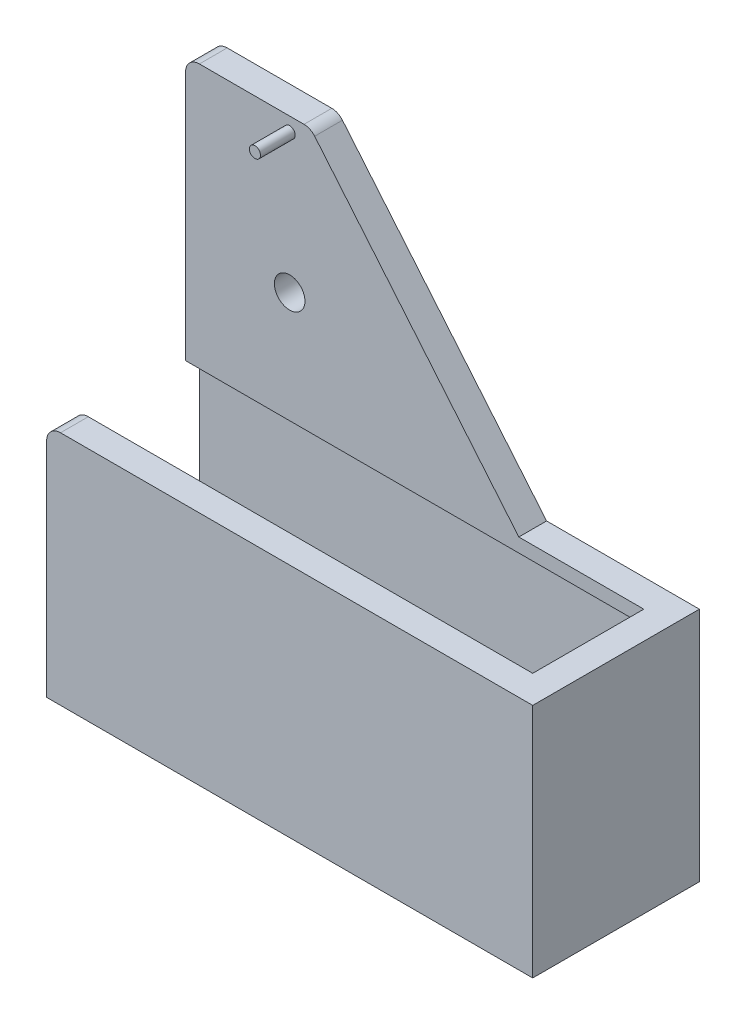
SolidWorks part; units mm, degrees
ref_plane "Front Plane" through (0, 0, 0) normal (0, 0, 1) x (1, 0, 0)
ref_plane "Top Plane" through (0, 0, 0) normal (0, 1, 0) x (1, 0, 0)
ref_plane "Right Plane" through (0, 0, 0) normal (1, 0, 0) x (0, 0, -1)
sketch "Sketch1" plane through (0, 0, 0) normal (0, 1, 0) x (1, 0, 0)
  line L1 (-165, 60) -> (165, 60)
  line L2 (-165, 60) -> (-165, -60)
  line L3 (-165, -60) -> (165, -60)
  line L4 (165, 60) -> (165, -60)
  line L5 (-165, 60) -> (165, -60) construction
  line L6 (-165, -60) -> (165, 60) construction
  point P0 (0, 0)
  dimension "D1" = 120
  dimension "D2" = 330
extrude "Boss-Extrude1" add sketch "Sketch1" along normal blind 120
sketch "Sketch2" plane through (165, 0, 0) normal (1, 0, 0) x (0, 0, -1)
  line L0 (0, 120) -> (0, 0) construction
  line L1 (-60, 120) -> (60, 120) construction
  line L2 (-60, 60) -> (60, 60) construction
  line L3 (-60, 120) -> (-60, 0) construction
  line L4 (60, 120) -> (60, 0) construction
  line L6 (-50, 110) -> (50, 110)
  line L7 (-50, 110) -> (-50, 10)
  line L8 (-50, 10) -> (50, 10)
  line L9 (50, 110) -> (50, 10)
  line L10 (-50, 110) -> (50, 10) construction
  line L11 (-50, 10) -> (50, 110) construction
  point P12 (0, 60)
  dimension "D1" = 100
  dimension "D2" = 100
extrude "Cut-Extrude1" cut sketch "Sketch2" against normal through all contours L7 L6 L9 L8
sketch "Sketch5" plane through (0, 120, 0) normal (0, 1, 0) x (1, 0, 0)
  line L0 (-165, -40) -> (165, -40)
  line L1 (-165, 60) -> (-165, -60) construction
  line L2 (165, -60) -> (165, 60) construction
  line L3 (-165, -40) -> (-165, 40)
  line L4 (-165, 40) -> (165, 40)
  line L5 (165, 40) -> (165, -40)
  line L6 (165, 60) -> (-165, 60) construction
  line L7 (-165, -60) -> (165, -60) construction
  dimension "D1" = 20
  dimension "D2" = 20
extrude "Cut-Extrude2" cut sketch "Sketch5" against normal up to next
sketch "Sketch6" plane through (0, 120, 0) normal (0, 1, 0) x (1, 0, 0)
  line L0 (-115, 60) -> (-75, 60)
  line L1 (165, 60) -> (-165, 60) construction
  line L2 (-75, 60) -> (-75, 40)
  line L3 (165, 40) -> (-165, 40) construction
  line L4 (-75, 40) -> (-115, 40)
  line L5 (-115, 40) -> (-115, 60)
  line L6 (-165, 60) -> (-165, 40) construction
  dimension "D1" = 40
  dimension "D2" = 50
extrude "Boss-Extrude2" add sketch "Sketch6" along normal blind 180
sketch "Sketch9" plane through (0, 0, -40) normal (0, 0, 1) x (1, 0, 0)
  line L0 (-90, 300) -> (-90, 290) construction
  line L1 (-115, 300) -> (-75, 300) construction
  line L2 (-90, 290) -> (-115, 290) construction
  line L3 (-115, 120) -> (-115, 300) construction
  line L4 (-75, 190) -> (-90, 190) construction
  line L5 (-75, 300) -> (-75, 120) construction
  line L6 (-90, 190) -> (-90, 226.184) construction
  line L7 (-115, 300) -> (-115, 120) construction
  circle A0 centre (-90, 290) radius 4
  circle A1 centre (-90, 190) radius 11
  point P4 (-102.5, 290)
  dimension "D3" = 8
  dimension "D6" = 22
  dimension "D1" = 25
  dimension "D2" = 10
  dimension "D4" = 100
extrude "Boss-Extrude3" add sketch "Sketch9" along normal blind 25 contours A0 region at (-90, 290, -40)
sketch "Sketch11" plane through (0, 120, 0) normal (0, 1, 0) x (1, 0, 0)
  line L0 (165, 60) -> (165, -60)
extrude "Extrude-Thin1" add sketch "Sketch11" against normal through all thin thin type one direction reverse wall 20
sketch "Sketch12" plane through (0, 0, 0) normal (0, -1, 0) x (1, 0, 0)
  line L0 (185, -60) -> (185, 60) construction
  line L1 (135, 50) -> (165, 50)
  line L2 (135, 50) -> (135, -50)
  line L3 (135, -50) -> (165, -50)
  line L4 (165, 50) -> (165, -50)
  line L5 (135, 50) -> (165, -50) construction
  line L6 (135, -50) -> (165, 50) construction
  line L7 (185, -60) -> (-165, -60) construction
  line L8 (-165, 60) -> (185, 60) construction
  point P0 (150, 0)
  dimension "D1" = 20
  dimension "D2" = 10
  dimension "D3" = 10
  dimension "D4" = 30
extrude "Cut-Extrude3" cut sketch "Sketch12" against normal up to next
sketch "Sketch14" plane through (0, 0, 0) normal (0, -1, 0) x (1, 0, 0)
  line L5 (-165, -60) -> (185, -60)
  line L12 (-165, -60) -> (185, -60)
  line L13 (185, -60) -> (185, 60)
  line L14 (185, -60) -> (185, 60)
  line L15 (185, 60) -> (-165, 60)
  line L19 (185, 60) -> (-165, 60)
  line L20 (-165, 60) -> (-165, -60)
  dimension "D1" = 0
extrude "Extrude-Thin2" add sketch "Sketch14" along normal blind 50 thin thin type one direction reverse wall 10
sketch "Sketch15" plane through (175, 0, 0) normal (-1, 0, 0) x (0, 0, 1)
  line L0 (-50, -50) -> (50, -50) construction
  line L1 (-50, -50) -> (50, -50)
sketch "Sketch16" plane through (0, 0, -40) normal (0, 0, 1) x (1, 0, 0)
  line L0 (-75, 300) -> (75, 120)
  line L1 (165, 120) -> (-75, 120) construction
  line L2 (75, 120) -> (-75, 120)
  line L3 (-75, 120) -> (-75, 300)
  dimension "D1" = 150
extrude "Boss-Extrude5" add sketch "Sketch16" against normal through all
fillet "Fillet1" radius 10 1 edges at (-75, 300, -50)
extrude "Cut-Extrude4" cut sketch "Sketch9<4>" against normal through all contours A1 region at (-90, 190, -40)
sketch "Sketch9<4>" plane through (0, 0, -40) normal (0, 0, 1) x (1, 0, 0) same geometry as "Sketch9"
sketch "Sketch17" plane through (0, 120, 0) normal (0, 1, 0) x (1, 0, 0)
  line L4 (-165, 40) -> (-115, 40)
  line L5 (-115, 40) -> (-115, 60)
  line L6 (-115, 60) -> (-165, 60)
  line L8 (-165, 40) -> (-115, 40)
  line L10 (-115, 60) -> (-165, 60)
  line L13 (-165, 60) -> (-165, 40)
  line L14 (-165, 60) -> (-165, 40)
  line L18 (-115, 40) -> (-115, 60)
  dimension "D1" = 0
extrude "Boss-Extrude6" add sketch "Sketch17" along normal through all
fillet "Fillet6" radius 10 2 edges at (-165, 120, 50) (-165, 300, -50)
